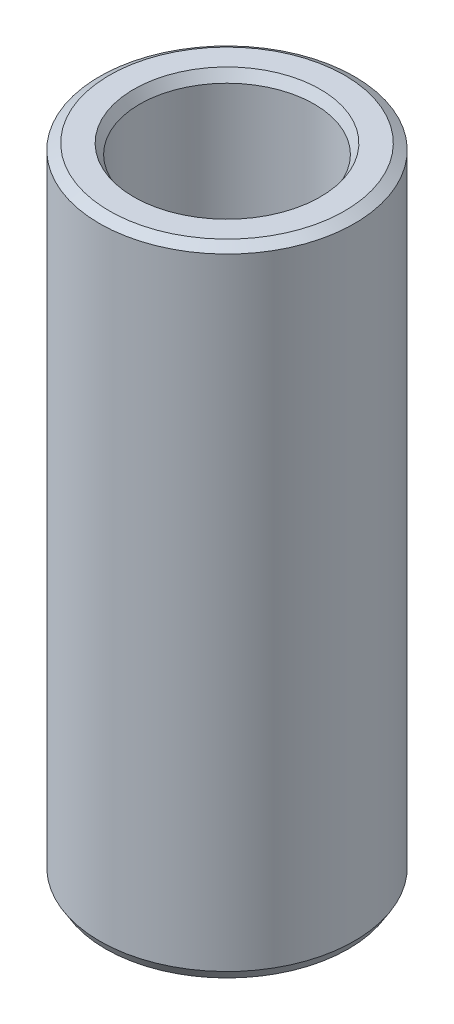
SolidWorks part; units mm, degrees
ref_plane "Front Plane" through (0, 0, 0) normal (0, 0, 1) x (1, 0, 0)
ref_plane "Top Plane" through (0, 0, 0) normal (0, 1, 0) x (1, 0, 0)
ref_plane "Right Plane" through (0, 0, 0) normal (1, 0, 0) x (0, 0, -1)
sketch "Sketch1" plane through (0, 0, 0) normal (0, 1, 0) x (1, 0, 0)
  circle A0 centre (0, 0) radius 45
  dimension "SLEEVE_OD" = 90
extrude "Boss-Extrude1" add sketch "Sketch1" along normal blind 224.9774
sketch "Sketch2" plane through (0, 0, 0) normal (0, 1, 0) x (1, 0, 0)
  circle A0 centre (0, 0) radius 30.8155
  dimension "BORE_D" = 61.6311
extrude "Cut-Extrude1" cut sketch "Sketch2" along normal through all
chamfer "Chamfer1" distance 2.1198 angle 58.602 4 edges at (0, 224.9774, 30.8155) (0, 0, 30.8155) (0, 0, 45) (0, 224.9774, 45) first distance on face at (0, 224.9774, 30.8155) first distance on face at (0, 0, 30.8155) first distance on face at (0, 224.9774, 45)
